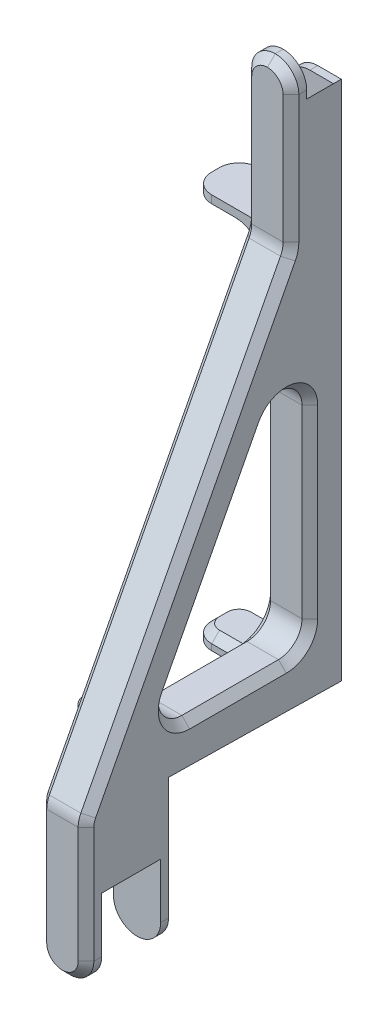
SolidWorks part; units mm, degrees
ref_plane "Front Plane" through (0, 0, 0) normal (0, 0, 1) x (1, 0, 0)
ref_plane "Top Plane" through (0, 0, 0) normal (0, 1, 0) x (1, 0, 0)
ref_plane "Right Plane" through (0, 0, 0) normal (1, 0, 0) x (0, 0, -1)
sketch "Sketch1" plane through (0, 0, 0) normal (1, 0, 0) x (0, 0, -1)
  line L0 (-5.08, -40.64) -> (-13.716, -40.64)
  line L1 (-5.08, -40.64) -> (-5.08, 0)
  line L2 (-5.08, 0) -> (0, 0)
  line L3 (0, 0) -> (0, -167.64)
  line L4 (-13.716, -40.64) -> (-13.716, 10.16)
  line L5 (-13.716, 10.16) -> (-18.796, 10.16)
  line L7 (-85.09, -167.64) -> (-85.09, -214.63)
  line L8 (-85.09, -214.63) -> (-80.01, -214.63)
  line L9 (-80.01, -214.63) -> (-80.01, -189.23)
  line L10 (-80.01, -189.23) -> (-60.96, -189.23)
  line L11 (-60.96, -189.23) -> (-60.96, -214.63)
  line L12 (-60.96, -214.63) -> (-55.88, -214.63)
  line L13 (-55.88, -214.63) -> (-55.88, -167.64)
  line L14 (-55.88, -167.64) -> (0, -167.64)
  line L15 (-18.796, 10.16) -> (-18.796, -40.64)
  line L17 (-85.09, -167.64) -> (-18.796, -40.64)
  line L21 (-64.1344, -154.94) -> (-12.7, -56.4066)
  line L22 (-12.7, -56.4066) -> (-12.7, -154.94)
  line L23 (-12.7, -154.94) -> (-64.1344, -154.94)
  line L24 (-38.4172, -105.6733) -> (-49.6756, -99.7964) construction
  line L25 (-38.4172, -154.94) -> (-38.4172, -167.64) construction
  line L26 (-12.7, -105.6733) -> (0, -105.6733) construction
  dimension "D1" = 5.08
  dimension "D2" = 127
  dimension "D3" = 50.8
  dimension "D4" = 19.05
  dimension "D5" = 21.59
  dimension "D6" = 8.636
  dimension "D7" = 40.64
  dimension "D8" = 12.7
  dimension "D9" = 25.4
  dimension "D10" = 50.8
extrude "Boss-Extrude1" add sketch "Sketch1" along normal mid plane 15.24
fillet "Fillet1" radius 7.62 12 edges at (0, -167.64, 85.09) (0, -56.4066, 12.7) (0, -154.94, 12.7) (0, -40.64, 18.796) (0, -154.94, 64.1344) (-7.62, 0, 2.54) (-7.62, 10.16, 16.256) (7.62, 10.16, 16.256) (-7.62, -214.63, 58.42) (7.62, -214.63, 58.42) (7.62, -214.63, 82.55) (-7.62, -214.63, 82.55)
sketch "Sketch2" plane through (7.62, 0, 0) normal (1, 0, 0) x (0, 0, -1)
  line L1 (-5.08, 0) -> (-13.716, 0)
  line L2 (-5.08, 0) -> (-5.08, -40.64)
  line L3 (-5.08, -40.64) -> (-13.716, -40.64)
  line L4 (-13.716, 0) -> (-13.716, -40.64)
extrude "Boss-Extrude2" add sketch "Sketch2" against normal blind 2.54
sketch "Sketch3" plane through (0, 0, 0) normal (0, 0, -1) x (-1, 0, 0)
  line L6 (7.62, -167.64) -> (27.94, -167.64)
  line L7 (7.62, -167.64) -> (7.62, -163.83)
  line L8 (7.62, -163.83) -> (27.94, -163.83)
  line L9 (27.94, -167.64) -> (27.94, -163.83)
  line L10 (7.62, -40.64) -> (27.94, -40.64)
  line L11 (7.62, -40.64) -> (7.62, -45.72)
  line L12 (7.62, -45.72) -> (27.94, -45.72)
  line L13 (27.94, -40.64) -> (27.94, -45.72)
  dimension "D1" = 3.81
  dimension "D2" = 20.32
  dimension "D3" = 5.08
extrude "Boss-Extrude3" add sketch "Sketch3" against normal blind 15.24
sketch "Sketch6" plane through (0, -167.64, 0) normal (0, -1, 0) x (-1, 0, 0)
  line L0 (7.62, -55.88) -> (7.62, -15.24) construction
  line L1 (7.62, -40.64) -> (27.94, -40.64)
  line L2 (7.62, -40.64) -> (7.62, -55.88)
  line L3 (7.62, -55.88) -> (27.94, -55.88)
  line L4 (27.94, -40.64) -> (27.94, -55.88)
  line L5 (27.94, -15.24) -> (27.94, 0) construction
  line L6 (7.62, -15.24) -> (27.94, -15.24) construction
  point P10 (7.62, -55.88)
extrude "Boss-Extrude5" add sketch "Sketch6" against normal up to surface (3.81 mm away) up to face at (-17.78, -163.83, 7.62)
fillet "Fillet2" radius 6.35 9 edges at (-27.94, -165.735, 15.24) (-27.94, -165.735, 0) (-7.62, -163.83, 7.62) (-27.94, -43.18, 15.24) (-27.94, -43.18, 0) (-7.62, -45.72, 7.62) (-7.62, -163.83, 48.26) (-27.94, -165.735, 40.64) (-27.94, -165.735, 55.88)
sketch "Sketch4" plane through (7.62, 0, 0) normal (1, 0, 0) x (0, 0, -1)
  line L0 (-55.88, -167.64) -> (0, -168.6154)
  line L1 (0, -168.6154) -> (0, -167.64)
  line L2 (-55.88, -167.64) -> (0, -167.64)
  dimension "D1" = 1
extrude "Boss-Extrude4" add sketch "Sketch4" against normal blind 50.8
sketch "Sketch5" plane through (0, -167.64, 0) normal (0, 1, 0) x (1, 0, 0)
  line L5 (-7.62, -40.64) -> (-7.62, -15.24)
  line L6 (-7.62, -15.24) -> (-21.59, -15.24)
  line L7 (-21.59, 0) -> (-43.18, 0)
  line L8 (-43.18, 0) -> (-43.18, -55.88)
  line L9 (-43.18, -55.88) -> (-21.59, -55.88)
  line L10 (-7.62, -40.64) -> (-7.62, -15.24)
  line L11 (-7.62, -15.24) -> (-21.59, -15.24)
  line L12 (-21.59, 0) -> (-43.18, 0)
  line L13 (-43.18, 0) -> (-43.18, -55.88)
  line L14 (-43.18, -55.88) -> (-21.59, -55.88)
  line L19 (-21.59, -40.64) -> (-7.62, -40.64)
  line L20 (-21.59, -40.64) -> (-7.62, -40.64)
  line L21 (-27.94, -49.53) -> (-27.94, -46.99)
  line L22 (-27.94, -49.53) -> (-27.94, -46.99)
  line L23 (-27.94, -8.89) -> (-27.94, -6.35)
  line L24 (-27.94, -8.89) -> (-27.94, -6.35)
  arc A2 (-27.94, -8.89) -> (-21.59, -15.24) centre (-21.59, -8.89) ccw
  arc A3 (-21.59, 0) -> (-27.94, -6.35) centre (-21.59, -6.35) ccw
  arc A4 (-27.94, -8.89) -> (-21.59, -15.24) centre (-21.59, -8.89) ccw
  arc A5 (-21.59, 0) -> (-27.94, -6.35) centre (-21.59, -6.35) ccw
  arc A8 (-27.94, -49.53) -> (-21.59, -55.88) centre (-21.59, -49.53) ccw
  arc A9 (-27.94, -49.53) -> (-21.59, -55.88) centre (-21.59, -49.53) ccw
  arc A10 (-21.59, -40.64) -> (-27.94, -46.99) centre (-21.59, -46.99) ccw
  arc A11 (-21.59, -40.64) -> (-27.94, -46.99) centre (-21.59, -46.99) ccw
  dimension "D1" = 0
extrude "Cut-Extrude1" cut sketch "Sketch5" against normal blind 50.8
chamfer "Chamfer1" distance 2.54 angle 45 57 edges at (-9.4799, -161.9701, 15.24) (-17.78, -163.83, 15.24) (-26.0801, -163.83, 13.3801) (-26.0801, -163.83, 1.8599) (-17.78, -163.83, 0) (3.81, 0, 0) (-9.4799, -161.9701, 0) (-5.3882, -2.2318, 0) (-7.62, -104.775, 0) (-7.62, -24.13, 0) (7.62, -84.3077, 0) (7.62, -188.2596, 85.09) (7.62, -167.6938, 84.8706) (7.62, -104.14, 51.943) (7.62, -40.5862, 19.0154) (7.62, -18.1154, 18.796) (5.3882, 7.9282, 18.796) (-5.3882, 7.9282, 18.796) (-7.62, -18.1154, 18.796) (-7.62, -188.2596, 85.09) (-7.62, -40.5862, 19.0154) (-7.62, -167.6938, 84.8706) (-7.62, -104.14, 51.943) (7.62, -80.0705, 18.5047) (7.62, -113.8694, 42.6956) (7.62, -117.3956, 12.7) (7.62, -151.2694, 58.0778) (7.62, -152.7082, 14.9318) (7.62, -154.94, 35.9405) (-7.62, -152.7082, 14.9318) (-7.62, -117.3956, 12.7) (-7.62, -154.94, 35.9405) (-7.62, -80.0705, 18.5047) (-7.62, -151.2694, 58.0778) (-7.62, -113.8694, 42.6956) (5.08, 0, 9.398) (-9.4799, -47.5799, 15.24) (-17.78, -45.72, 15.24) (-26.0801, -45.72, 13.3801) (-26.0801, -45.72, 1.8599) (-17.78, -45.72, 0) (-9.4799, -47.5799, 0) (5.3882, -212.3982, 85.09) (-5.3882, -212.3982, 85.09) (-27.94, -163.83, 7.62) (-27.94, -45.72, 7.62) (-9.4799, -161.9701, 55.88) (-17.78, -163.83, 55.88) (-26.0801, -163.83, 54.0201) (-27.94, -163.83, 48.26) (-26.0801, -163.83, 42.4999) (-9.4799, -161.9701, 40.64) (-17.78, -163.83, 40.64) (7.62, -187.325, 55.88) (5.3882, -212.3982, 55.88) (-5.3882, -212.3982, 55.88) (-7.62, -187.325, 55.88)
